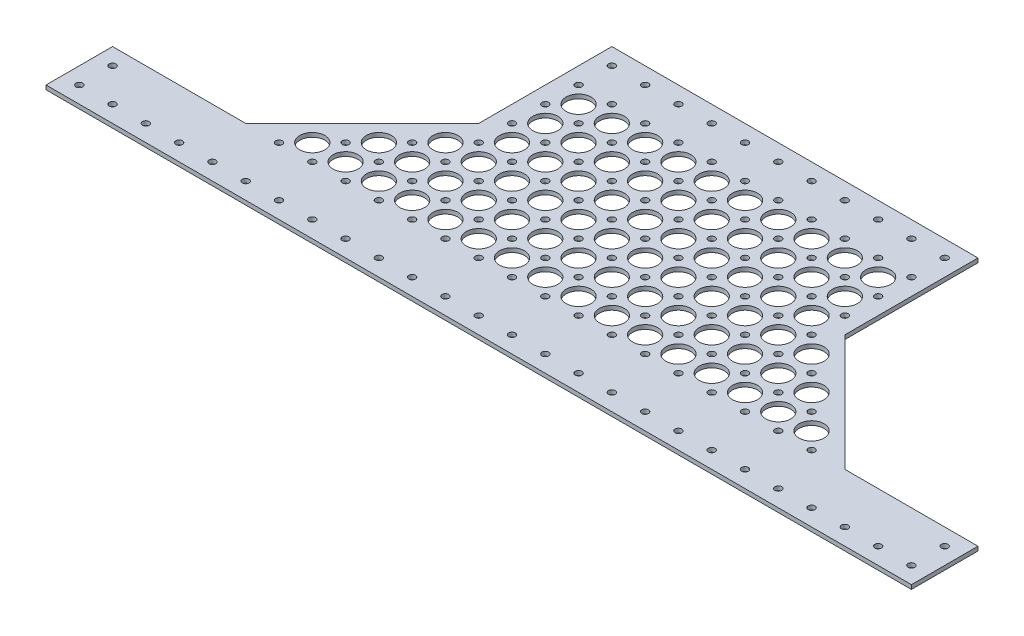
SolidWorks part; units mm, degrees
ref_plane "Front Plane" through (0, 0, 0) normal (0, 0, 1) x (1, 0, 0)
ref_plane "Top Plane" through (0, 0, 0) normal (0, 1, 0) x (1, 0, 0)
ref_plane "Right Plane" through (0, 0, 0) normal (1, 0, 0) x (0, 0, -1)
sketch "Sketch1" plane through (0, 0, 0) normal (0, 1, 0) x (1, 0, 0)
  line L0 (0, 0) -> (0, 101.6)
  line L1 (0, 101.6) -> (279.4, 101.6)
  line L2 (279.4, 101.6) -> (279.4, 0)
  line L3 (279.4, 0) -> (368.3045, -88.9045)
  line L4 (368.3045, -88.9045) -> (469.9045, -88.9045)
  line L5 (469.9045, -88.9045) -> (469.9045, -419.1045)
  line L6 (469.9045, -419.1045) -> (368.3045, -419.1045)
  line L7 (368.3045, -419.1045) -> (279.4, -508.0091)
  line L8 (279.4, -508.0091) -> (279.4, -609.6091)
  line L9 (279.4, -609.6091) -> (0, -609.6091)
  line L10 (0, -609.6091) -> (0, -508.0091)
  line L11 (0, -508.0091) -> (-88.9045, -419.1045)
  line L12 (-88.9045, -419.1045) -> (-190.5045, -419.1045)
  line L13 (-190.5045, -419.1045) -> (-190.5045, -88.9045)
  line L14 (-190.5045, -88.9045) -> (-88.9045, -88.9045)
  line L15 (-88.9045, -88.9045) -> (0, 0)
  line L16 (-190.5045, -88.9045) -> (-177.8045, -88.9045)
  line L17 (-177.8045, -88.9045) -> (-177.8045, -419.1045) construction
  line L18 (-177.8045, -419.1045) -> (-190.5045, -419.1045)
  line L19 (-177.8045, -101.6045) -> (-177.8045, -127.0045) construction
  line L20 (139.7, -898.4) -> (139.7, 49101.6) construction
  line L21 (-966.4523, 88.9) -> (49033.5477, 88.9) construction
  line L22 (12.7, 88.9) -> (38.1, 88.9) construction
  line L23 (-1190.5045, -254.0045) -> (48809.4955, -254.0045) construction
  line L24 (-190.5045, -368.3045) -> (-88.9045, -368.3045) construction
  line L25 (-88.9045, -368.3045) -> (-88.9045, -419.1045) construction
  line L26 (-101.6045, -406.4045) -> (-127.0045, -406.4045) construction
  line L27 (-101.6045, -381.0045) -> (-127.0045, -381.0045) construction
  line L28 (-1102.5698, -114.3045) -> (48897.4302, -114.3045) construction
  line L29 (-1089.6596, -165.1045) -> (48910.3404, -165.1045) construction
  line L30 (-177.8045, -127.0045) -> (-152.4045, -127.0045) construction
  circle A0 centre (-177.8045, -101.6045) radius 2.54
  circle A1 centre (-177.8045, -127.0045) radius 2.54
  circle A2 centre (-177.8045, -152.4045) radius 2.54
  circle A3 centre (-177.8045, -177.8045) radius 2.54
  circle A4 centre (-177.8045, -203.2045) radius 2.54
  circle A5 centre (-177.8045, -228.6045) radius 2.54
  circle A6 centre (-177.8045, -254.0045) radius 2.54
  circle A7 centre (-177.8045, -279.4045) radius 2.54
  circle A8 centre (-177.8045, -304.8045) radius 2.54
  circle A9 centre (-177.8045, -330.2045) radius 2.54
  circle A10 centre (-177.8045, -355.6045) radius 2.54
  circle A11 centre (-177.8045, -381.0045) radius 2.54
  circle A12 centre (-177.8045, -406.4045) radius 2.54
  circle A13 centre (457.2045, -406.4045) radius 2.54
  circle A14 centre (457.2045, -381.0045) radius 2.54
  circle A15 centre (457.2045, -355.6045) radius 2.54
  circle A16 centre (457.2045, -330.2045) radius 2.54
  circle A17 centre (457.2045, -304.8045) radius 2.54
  circle A18 centre (457.2045, -279.4045) radius 2.54
  circle A19 centre (457.2045, -254.0045) radius 2.54
  circle A20 centre (457.2045, -228.6045) radius 2.54
  circle A21 centre (457.2045, -152.4045) radius 2.54
  circle A22 centre (457.2045, -177.8045) radius 2.54
  circle A23 centre (457.2045, -203.2045) radius 2.54
  circle A24 centre (457.2045, -127.0045) radius 2.54
  circle A25 centre (457.2045, -101.6045) radius 2.54
  circle A26 centre (12.7, 88.9) radius 2.54
  circle A27 centre (38.1, 88.9) radius 2.54
  circle A28 centre (63.5, 88.9) radius 2.54
  circle A29 centre (88.9, 88.9) radius 2.54
  circle A30 centre (114.3, 88.9) radius 2.54
  circle A31 centre (139.7, 88.9) radius 2.54
  circle A32 centre (165.1, 88.9) radius 2.54
  circle A33 centre (190.5, 88.9) radius 2.54
  circle A34 centre (215.9, 88.9) radius 2.54
  circle A35 centre (241.3, 88.9) radius 2.54
  circle A36 centre (266.7, 88.9) radius 2.54
  circle A37 centre (266.7, -596.9091) radius 2.54
  circle A38 centre (241.3, -596.9091) radius 2.54
  circle A39 centre (215.9, -596.9091) radius 2.54
  circle A40 centre (190.5, -596.9091) radius 2.54
  circle A41 centre (165.1, -596.9091) radius 2.54
  circle A42 centre (139.7, -596.9091) radius 2.54
  circle A43 centre (114.3, -596.9091) radius 2.54
  circle A44 centre (88.9, -596.9091) radius 2.54
  circle A45 centre (63.5, -596.9091) radius 2.54
  circle A46 centre (38.1, -596.9091) radius 2.54
  circle A47 centre (12.7, -596.9091) radius 2.54
  circle A48 centre (-101.6045, -381.0045) radius 2.54
  circle A49 centre (-101.6045, -406.4045) radius 2.54
  circle A50 centre (381.0045, -406.4045) radius 2.54
  circle A51 centre (381.0045, -381.0045) radius 2.54
  circle A52 centre (-127.0045, -406.4045) radius 2.54
  circle A53 centre (-152.4045, -406.4045) radius 2.54
  circle A54 centre (-127.0045, -381.0045) radius 2.54
  circle A55 centre (-152.4045, -381.0045) radius 2.54
  circle A56 centre (431.8045, -381.0045) radius 2.54
  circle A57 centre (406.4045, -381.0045) radius 2.54
  circle A58 centre (431.8045, -406.4045) radius 2.54
  circle A59 centre (406.4045, -406.4045) radius 2.54
  circle A60 centre (-152.4045, -127.0045) radius 2.54
  circle A61 centre (-152.4045, -152.4045) radius 2.54
  circle A62 centre (-127.0045, -127.0045) radius 2.54
  circle A63 centre (-127.0045, -152.4045) radius 2.54
  circle A64 centre (-101.6045, -127.0045) radius 2.54
  circle A65 centre (-101.6045, -152.4045) radius 2.54
  circle A66 centre (-76.2045, -127.0045) radius 2.54
  circle A67 centre (-76.2045, -152.4045) radius 2.54
  circle A68 centre (-50.8045, -127.0045) radius 2.54
  circle A69 centre (-50.8045, -152.4045) radius 2.54
  circle A70 centre (-25.4045, -127.0045) radius 2.54
  circle A71 centre (-25.4045, -152.4045) radius 2.54
  circle A72 centre (-0.0045, -127.0045) radius 2.54
  circle A73 centre (-0.0045, -152.4045) radius 2.54
  circle A74 centre (25.3955, -127.0045) radius 2.54
  circle A75 centre (25.3955, -152.4045) radius 2.54
  circle A76 centre (50.7955, -127.0045) radius 2.54
  circle A77 centre (50.7955, -152.4045) radius 2.54
  circle A78 centre (76.1955, -127.0045) radius 2.54
  circle A79 centre (76.1955, -152.4045) radius 2.54
  circle A80 centre (101.5955, -127.0045) radius 2.54
  circle A81 centre (101.5955, -152.4045) radius 2.54
  circle A82 centre (126.9955, -127.0045) radius 2.54
  circle A83 centre (126.9955, -152.4045) radius 2.54
  circle A84 centre (152.3955, -127.0045) radius 2.54
  circle A85 centre (152.3955, -152.4045) radius 2.54
  circle A86 centre (177.7955, -127.0045) radius 2.54
  circle A87 centre (177.7955, -152.4045) radius 2.54
  circle A88 centre (203.1955, -127.0045) radius 2.54
  circle A89 centre (203.1955, -152.4045) radius 2.54
  circle A90 centre (228.5955, -127.0045) radius 2.54
  circle A91 centre (228.5955, -152.4045) radius 2.54
  circle A92 centre (253.9955, -127.0045) radius 2.54
  circle A93 centre (253.9955, -152.4045) radius 2.54
  circle A94 centre (279.3955, -127.0045) radius 2.54
  circle A95 centre (279.3955, -152.4045) radius 2.54
  circle A96 centre (304.7955, -127.0045) radius 2.54
  circle A97 centre (304.7955, -152.4045) radius 2.54
  circle A98 centre (330.1955, -127.0045) radius 2.54
  circle A99 centre (330.1955, -152.4045) radius 2.54
  circle A100 centre (355.5955, -127.0045) radius 2.54
  circle A101 centre (355.5955, -152.4045) radius 2.54
  circle A102 centre (380.9955, -127.0045) radius 2.54
  circle A103 centre (380.9955, -152.4045) radius 2.54
  circle A104 centre (406.3955, -127.0045) radius 2.54
  circle A105 centre (406.3955, -152.4045) radius 2.54
  circle A106 centre (431.7955, -127.0045) radius 2.54
  circle A107 centre (431.7955, -152.4045) radius 2.54
  point P50 (139.7, 101.6)
  point P105 (-190.5045, -254.0045)
  dimension "D11" = 5.08
  dimension "D16" = 5.08
  dimension "D21" = 5.08
  dimension "D22" = 5.08
  dimension "D1" = 135
  dimension "D2" = 135
  dimension "D3" = 135
  dimension "D4" = 135
  dimension "D5" = 101.6
  dimension "D6" = 279.4
  dimension "D7" = 330.2
  dimension "D8" = 101.6
  dimension "D9" = 125.73
  dimension "D10" = 12.7
  dimension "D12" = 12.7
  dimension "D13" = 25.4
  dimension "D15" = 12.7
  dimension "D17" = 12.7
  dimension "D18" = 25.4
  dimension "D19" = 101.6
  dimension "D20" = 50.8
  dimension "D23" = 12.7
  dimension "D24" = 12.7
  dimension "D25" = 12.7
  dimension "D26" = 12.7
  dimension "D27" = 25.4
  dimension "D28" = 25.4
  dimension "D29" = 25.4
  dimension "D30" = 50.8
  dimension "D31" = 25.4
  dimension "D14" = 13
extrude "Boss-Extrude1" add sketch "Sketch1" along normal blind 3.175 contours L15 L14 L13 L12 L11 L10 L9 L8 L7 L6 L5 L4 L3 L2 L1 L0 A107 A106 A105 A104 A103 A102 A101 A100 A99 A98 A97 A96 A95 A94 A93 A92 region at (139.7, 0, 254.2329)
sketch "Sketch2" plane through (0, 0, 609.6091) normal (0, 0, 1) x (1, 0, 0)
  line L0 (279.4, 0) -> (0, 0) construction
  line L1 (-203.0133, -12.7) -> (508.1867, -12.7)
  line L2 (-203.0133, -12.7) -> (-203.0133, 12.7)
  line L3 (-203.0133, 12.7) -> (508.1867, 12.7)
  line L4 (508.1867, -12.7) -> (508.1867, 12.7)
  line L5 (-203.0133, -12.7) -> (508.1867, 12.7) construction
  line L6 (-203.0133, 12.7) -> (508.1867, -12.7) construction
  point P0 (152.5867, 0)
  dimension "D1" = 711.2
  dimension "D2" = 25.4
extrude "Cut-Extrude2" cut sketch "Sketch2" against normal blind 469.9
sketch "Sketch3" plane through (0, 3.175, 0) normal (0, 1, 0) x (1, 0, 0)
  line L0 (12.7, 88.9) -> (38.1, 88.9) construction
  line L1 (12.7, 88.9) -> (12.7, 63.5) construction
  line L2 (0, 0) -> (0, 101.6) construction
  line L3 (12.7, -88.9) -> (-12.7, -88.9) construction
  line L4 (12.7, -63.5) -> (-12.7, -63.5) construction
  line L5 (12.7, -38.1) -> (-12.7, -38.1) construction
  line L6 (0, 101.6) -> (279.4, 101.6) construction
  line L7 (266.7, -88.9) -> (292.1, -88.9) construction
  line L8 (266.7, -63.5) -> (292.1, -63.5) construction
  line L9 (266.7, -38.1) -> (292.1, -38.1) construction
  line L10 (25.4, 50.8) -> (50.8, 50.8) construction
  line L11 (25.4, 50.8) -> (25.4, 25.4) construction
  line L12 (279.4, 101.6) -> (279.4, 0) construction
  line L13 (25.4, -25.4) -> (0, -25.4) construction
  circle A0 centre (12.7, 88.9) radius 2.54
  circle A1 centre (38.1, 88.9) radius 2.54
  circle A2 centre (63.5, 88.9) radius 2.54
  circle A3 centre (88.9, 88.9) radius 2.54
  circle A4 centre (114.3, 88.9) radius 2.54
  circle A5 centre (139.7, 88.9) radius 2.54
  circle A6 centre (165.1, 88.9) radius 2.54
  circle A7 centre (190.5, 88.9) radius 2.54
  circle A8 centre (215.9, 88.9) radius 2.54
  circle A9 centre (241.3, 88.9) radius 2.54
  circle A10 centre (266.7, 88.9) radius 2.54
  circle A18 centre (12.7, 63.5) radius 2.54
  circle A19 centre (38.1, 63.5) radius 2.54
  circle A20 centre (63.5, 63.5) radius 2.54
  circle A21 centre (88.9, 63.5) radius 2.54
  circle A22 centre (114.3, 63.5) radius 2.54
  circle A23 centre (139.7, 63.5) radius 2.54
  circle A24 centre (165.1, 63.5) radius 2.54
  circle A25 centre (190.5, 63.5) radius 2.54
  circle A26 centre (215.9, 63.5) radius 2.54
  circle A27 centre (241.3, 63.5) radius 2.54
  circle A28 centre (266.7, 63.5) radius 2.54
  circle A36 centre (12.7, 38.1) radius 2.54
  circle A37 centre (38.1, 38.1) radius 2.54
  circle A38 centre (63.5, 38.1) radius 2.54
  circle A39 centre (88.9, 38.1) radius 2.54
  circle A40 centre (114.3, 38.1) radius 2.54
  circle A41 centre (139.7, 38.1) radius 2.54
  circle A42 centre (165.1, 38.1) radius 2.54
  circle A43 centre (190.5, 38.1) radius 2.54
  circle A44 centre (215.9, 38.1) radius 2.54
  circle A45 centre (241.3, 38.1) radius 2.54
  circle A46 centre (266.7, 38.1) radius 2.54
  circle A54 centre (12.7, 12.7) radius 2.54
  circle A55 centre (38.1, 12.7) radius 2.54
  circle A56 centre (63.5, 12.7) radius 2.54
  circle A57 centre (88.9, 12.7) radius 2.54
  circle A58 centre (114.3, 12.7) radius 2.54
  circle A59 centre (139.7, 12.7) radius 2.54
  circle A60 centre (165.1, 12.7) radius 2.54
  circle A61 centre (190.5, 12.7) radius 2.54
  circle A62 centre (215.9, 12.7) radius 2.54
  circle A63 centre (241.3, 12.7) radius 2.54
  circle A64 centre (266.7, 12.7) radius 2.54
  circle A72 centre (12.7, -12.7) radius 2.54
  circle A73 centre (38.1, -12.7) radius 2.54
  circle A74 centre (63.5, -12.7) radius 2.54
  circle A75 centre (88.9, -12.7) radius 2.54
  circle A76 centre (114.3, -12.7) radius 2.54
  circle A77 centre (139.7, -12.7) radius 2.54
  circle A78 centre (165.1, -12.7) radius 2.54
  circle A79 centre (190.5, -12.7) radius 2.54
  circle A80 centre (215.9, -12.7) radius 2.54
  circle A81 centre (241.3, -12.7) radius 2.54
  circle A82 centre (266.7, -12.7) radius 2.54
  circle A90 centre (12.7, -38.1) radius 2.54
  circle A91 centre (38.1, -38.1) radius 2.54
  circle A92 centre (63.5, -38.1) radius 2.54
  circle A93 centre (88.9, -38.1) radius 2.54
  circle A94 centre (114.3, -38.1) radius 2.54
  circle A95 centre (139.7, -38.1) radius 2.54
  circle A96 centre (165.1, -38.1) radius 2.54
  circle A97 centre (190.5, -38.1) radius 2.54
  circle A98 centre (215.9, -38.1) radius 2.54
  circle A99 centre (241.3, -38.1) radius 2.54
  circle A100 centre (266.7, -38.1) radius 2.54
  circle A108 centre (12.7, -63.5) radius 2.54
  circle A109 centre (38.1, -63.5) radius 2.54
  circle A110 centre (63.5, -63.5) radius 2.54
  circle A111 centre (88.9, -63.5) radius 2.54
  circle A112 centre (114.3, -63.5) radius 2.54
  circle A113 centre (139.7, -63.5) radius 2.54
  circle A114 centre (165.1, -63.5) radius 2.54
  circle A115 centre (190.5, -63.5) radius 2.54
  circle A116 centre (215.9, -63.5) radius 2.54
  circle A117 centre (241.3, -63.5) radius 2.54
  circle A118 centre (266.7, -63.5) radius 2.54
  circle A126 centre (12.7, -88.9) radius 2.54
  circle A127 centre (38.1, -88.9) radius 2.54
  circle A128 centre (63.5, -88.9) radius 2.54
  circle A129 centre (88.9, -88.9) radius 2.54
  circle A130 centre (114.3, -88.9) radius 2.54
  circle A131 centre (139.7, -88.9) radius 2.54
  circle A132 centre (165.1, -88.9) radius 2.54
  circle A133 centre (190.5, -88.9) radius 2.54
  circle A134 centre (215.9, -88.9) radius 2.54
  circle A135 centre (241.3, -88.9) radius 2.54
  circle A136 centre (266.7, -88.9) radius 2.54
  circle A211 centre (-12.7, -88.9) radius 2.54
  circle A212 centre (-38.1, -88.9) radius 2.54
  circle A213 centre (-63.5, -88.9) radius 2.54
  circle A214 centre (-12.7, -63.5) radius 2.54
  circle A215 centre (-38.1, -63.5) radius 2.54
  circle A216 centre (-12.7, -38.1) radius 2.54
  circle A224 centre (292.1, -88.9) radius 2.54
  circle A225 centre (317.5, -88.9) radius 2.54
  circle A226 centre (342.9, -88.9) radius 2.54
  circle A227 centre (292.1, -63.5) radius 2.54
  circle A228 centre (317.5, -63.5) radius 2.54
  circle A229 centre (292.1, -38.1) radius 2.54
  circle A230 centre (25.4, 50.8) radius 9.525
  circle A231 centre (50.8, 50.8) radius 9.525
  circle A232 centre (292.1, 88.9) radius 2.54 [skipped]
  circle A233 centre (317.5, 88.9) radius 2.54 [skipped]
  circle A234 centre (342.9, 88.9) radius 2.54 [skipped]
  circle A235 centre (368.3, 88.9) radius 2.54 [skipped]
  circle A236 centre (393.7, 88.9) radius 2.54 [skipped]
  circle A237 centre (419.1, 88.9) radius 2.54 [skipped]
  circle A238 centre (444.5, 88.9) radius 2.54 [skipped]
  circle A239 centre (12.7, -114.3) radius 2.54 [skipped]
  circle A240 centre (38.1, -114.3) radius 2.54 [skipped]
  circle A241 centre (63.5, -114.3) radius 2.54 [skipped]
  circle A242 centre (88.9, -114.3) radius 2.54 [skipped]
  circle A243 centre (114.3, -114.3) radius 2.54 [skipped]
  circle A244 centre (139.7, -114.3) radius 2.54 [skipped]
  circle A245 centre (165.1, -114.3) radius 2.54 [skipped]
  circle A246 centre (190.5, -114.3) radius 2.54 [skipped]
  circle A247 centre (215.9, -114.3) radius 2.54 [skipped]
  circle A248 centre (241.3, -114.3) radius 2.54 [skipped]
  circle A249 centre (266.7, -114.3) radius 2.54 [skipped]
  circle A250 centre (76.2, 50.8) radius 9.525
  circle A251 centre (101.6, 50.8) radius 9.525
  circle A252 centre (127, 50.8) radius 9.525
  circle A253 centre (152.4, 50.8) radius 9.525
  circle A254 centre (177.8, 50.8) radius 9.525
  circle A255 centre (203.2, 50.8) radius 9.525
  circle A256 centre (228.6, 50.8) radius 9.525
  circle A257 centre (254, 50.8) radius 9.525
  circle A265 centre (50.8, 25.4) radius 9.525
  circle A266 centre (76.2, 25.4) radius 9.525
  circle A267 centre (101.6, 25.4) radius 9.525
  circle A268 centre (127, 25.4) radius 9.525
  circle A269 centre (152.4, 25.4) radius 9.525
  circle A270 centre (177.8, 25.4) radius 9.525
  circle A271 centre (203.2, 25.4) radius 9.525
  circle A272 centre (228.6, 25.4) radius 9.525
  circle A273 centre (254, 25.4) radius 9.525
  circle A281 centre (50.8, 0) radius 9.525
  circle A282 centre (76.2, 0) radius 9.525
  circle A283 centre (101.6, 0) radius 9.525
  circle A284 centre (127, 0) radius 9.525
  circle A285 centre (152.4, 0) radius 9.525
  circle A286 centre (177.8, 0) radius 9.525
  circle A287 centre (203.2, 0) radius 9.525
  circle A288 centre (228.6, 0) radius 9.525
  circle A289 centre (254, 0) radius 9.525
  circle A297 centre (50.8, -25.4) radius 9.525
  circle A298 centre (76.2, -25.4) radius 9.525
  circle A299 centre (101.6, -25.4) radius 9.525
  circle A300 centre (127, -25.4) radius 9.525
  circle A301 centre (152.4, -25.4) radius 9.525
  circle A302 centre (177.8, -25.4) radius 9.525
  circle A303 centre (203.2, -25.4) radius 9.525
  circle A304 centre (228.6, -25.4) radius 9.525
  circle A305 centre (254, -25.4) radius 9.525
  circle A306 centre (279.4, -25.4) radius 9.525
  circle A313 centre (50.8, -50.8) radius 9.525
  circle A314 centre (76.2, -50.8) radius 9.525
  circle A315 centre (101.6, -50.8) radius 9.525
  circle A316 centre (127, -50.8) radius 9.525
  circle A317 centre (152.4, -50.8) radius 9.525
  circle A318 centre (177.8, -50.8) radius 9.525
  circle A319 centre (203.2, -50.8) radius 9.525
  circle A320 centre (228.6, -50.8) radius 9.525
  circle A321 centre (254, -50.8) radius 9.525
  circle A322 centre (279.4, -50.8) radius 9.525
  circle A323 centre (304.8, -50.8) radius 9.525
  circle A329 centre (50.8, -76.2) radius 9.525
  circle A330 centre (76.2, -76.2) radius 9.525
  circle A331 centre (101.6, -76.2) radius 9.525
  circle A332 centre (127, -76.2) radius 9.525
  circle A333 centre (152.4, -76.2) radius 9.525
  circle A334 centre (177.8, -76.2) radius 9.525
  circle A335 centre (203.2, -76.2) radius 9.525
  circle A336 centre (228.6, -76.2) radius 9.525
  circle A337 centre (254, -76.2) radius 9.525
  circle A338 centre (279.4, -76.2) radius 9.525
  circle A339 centre (304.8, -76.2) radius 9.525
  circle A340 centre (330.2, -76.2) radius 9.525
  circle A345 centre (25.4, 25.4) radius 9.525
  circle A346 centre (25.4, 0) radius 9.525
  circle A347 centre (25.4, -25.4) radius 9.525
  circle A348 centre (25.4, -50.8) radius 9.525
  circle A349 centre (25.4, -76.2) radius 9.525
  circle A350 centre (279.4, 25.4) radius 9.525 [skipped]
  circle A351 centre (304.8, 25.4) radius 9.525 [skipped]
  circle A352 centre (330.2, 25.4) radius 9.525 [skipped]
  circle A353 centre (355.6, 25.4) radius 9.525 [skipped]
  circle A354 centre (381, 25.4) radius 9.525 [skipped]
  circle A355 centre (406.4, 25.4) radius 9.525 [skipped]
  circle A356 centre (431.8, 25.4) radius 9.525 [skipped]
  circle A357 centre (279.4, 0) radius 9.525 [skipped]
  circle A358 centre (304.8, 0) radius 9.525 [skipped]
  circle A359 centre (330.2, 0) radius 9.525 [skipped]
  circle A360 centre (355.6, 0) radius 9.525 [skipped]
  circle A361 centre (381, 0) radius 9.525 [skipped]
  circle A362 centre (406.4, 0) radius 9.525 [skipped]
  circle A363 centre (431.8, 0) radius 9.525 [skipped]
  circle A364 centre (304.8, 50.8) radius 9.525 [skipped]
  circle A365 centre (330.2, 50.8) radius 9.525 [skipped]
  circle A366 centre (355.6, 50.8) radius 9.525 [skipped]
  circle A367 centre (381, 50.8) radius 9.525 [skipped]
  circle A368 centre (406.4, 50.8) radius 9.525 [skipped]
  circle A369 centre (431.8, 50.8) radius 9.525 [skipped]
  circle A370 centre (279.4, 50.8) radius 9.525 [skipped]
  circle A371 centre (330.2, -25.4) radius 9.525 [skipped]
  circle A372 centre (355.6, -25.4) radius 9.525 [skipped]
  circle A373 centre (381, -25.4) radius 9.525 [skipped]
  circle A374 centre (406.4, -25.4) radius 9.525 [skipped]
  circle A375 centre (431.8, -25.4) radius 9.525 [skipped]
  circle A376 centre (381, -50.8) radius 9.525 [skipped]
  circle A377 centre (406.4, -50.8) radius 9.525 [skipped]
  circle A378 centre (431.8, -50.8) radius 9.525 [skipped]
  circle A379 centre (406.4, -76.2) radius 9.525 [skipped]
  circle A380 centre (431.8, -76.2) radius 9.525 [skipped]
  circle A381 centre (381, -76.2) radius 9.525 [skipped]
  circle A382 centre (355.6, -76.2) radius 9.525 [skipped]
  circle A383 centre (355.6, -50.8) radius 9.525 [skipped]
  circle A384 centre (330.2, -50.8) radius 9.525 [skipped]
  circle A385 centre (304.8, -25.4) radius 9.525 [skipped]
  circle A386 centre (0, -25.4) radius 9.525
  circle A387 centre (0, -50.8) radius 9.525
  circle A388 centre (0, -76.2) radius 9.525
  circle A390 centre (-25.4, -50.8) radius 9.525
  circle A391 centre (-25.4, -76.2) radius 9.525
  circle A394 centre (-50.8, -76.2) radius 9.525
  circle A395 centre (-50.8, -25.4) radius 9.525 [skipped]
  circle A396 centre (-50.8, -50.8) radius 9.525 [skipped]
  circle A397 centre (-25.4, -25.4) radius 9.525 [skipped]
  dimension "D1" = 5.08
  dimension "D6" = 19.05
  dimension "D2" = 25.4
  dimension "D4" = 25.4
  dimension "D7" = 25.4
  dimension "D8" = 25.4
  dimension "D9" = 25.4
  dimension "D10" = 25.4
  dimension "D11" = 25.4
  dimension "D12" = 25.4
  dimension "D13" = 25.4
  dimension "D14" = 50.8
  dimension "D16" = 25.4
  dimension "D17" = 25.4
  dimension "D19" = 25.4
  dimension "D20" = 25.4
  dimension "D3" = 18
  dimension "D5" = 9
  dimension "D18" = 17
  dimension "D15" = 6
  dimension "D21" = 4
extrude "Cut-Extrude3" cut sketch "Sketch3" against normal blind 3.175
